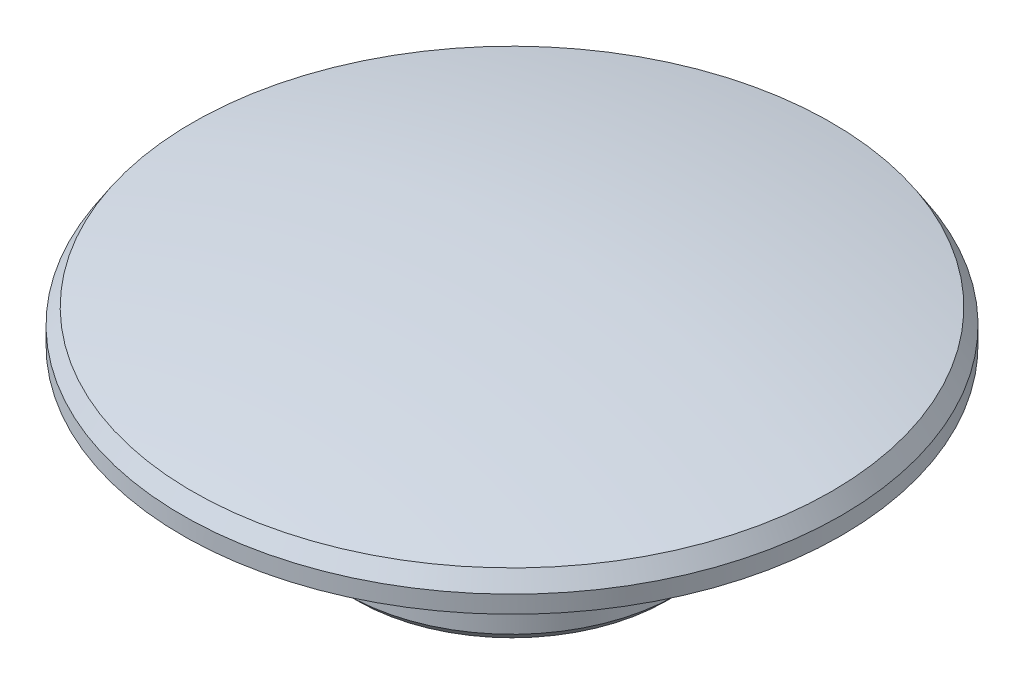
SolidWorks part; units mm, degrees
material "ABS"
ref_plane "正面" through (0, 0, 0) normal (0, 0, 1) x (1, 0, 0)
ref_plane "平面" through (0, 0, 0) normal (0, 1, 0) x (1, 0, 0)
ref_plane "右側面" through (0, 0, 0) normal (1, 0, 0) x (0, 0, -1)
sketch "ｽｹｯﾁ1" plane through (0, 0, 0) normal (0, 0, 1) x (1, 0, 0)
  line L0 (5.7, 0) -> (5.7, 8)
  line L1 (5.7, 8) -> (0, 8)
  line L2 (0, 8) -> (0, 10.23)
  line L3 (5.7, 0) -> (8, 0)
  line L4 (8, 0) -> (8, 7)
  line L5 (8, 7) -> (16, 7)
  line L6 (16, 7) -> (16, 8.5)
  arc A0 (0, 10.23) -> (16, 8.5) centre (0, -64.6234) cw
  dimension "D1" = 5.7
  dimension "D7" = 16
  dimension "D2" = 10.23
  dimension "D3" = 1
  dimension "D4" = 7
  dimension "D5" = 0
  dimension "D6" = 8
  dimension "D8" = 1.5
revolve "回転1" add sketch "ｽｹｯﾁ1" angle 360 about L2
chamfer "面取り1" distance 0.5 angle 45 1 edges at (16, 8.5, 0) first distance on face at (16, 8.5, 0)
chamfer "面取り2" distance 0.5 angle 45 2 edges at (5.7, 0, 0) (8, 0, 0)
